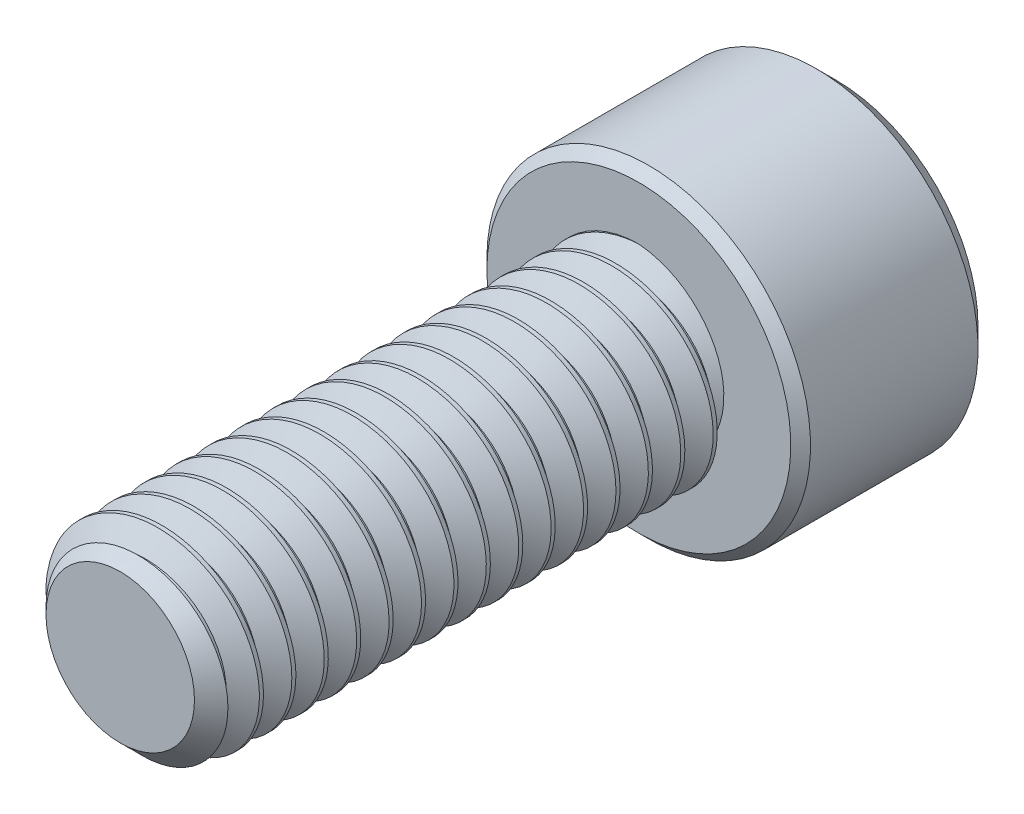
SolidWorks part; units mm, degrees
material "Cast Alloy Steel"
ref_plane "Front Plane" through (0, 0, 0) normal (0, 0, 1) x (1, 0, 0)
ref_plane "Top Plane" through (0, 0, 0) normal (0, 1, 0) x (1, 0, 0)
ref_plane "Right Plane" through (0, 0, 0) normal (1, 0, 0) x (0, 0, -1)
sketch "Sketch1" plane through (0, 0, 0) normal (0, 0, 1) x (1, 0, 0)
  line L0 (0, 2.413) -> (0, -2.413) construction
  circle A0 centre (0, 0) radius 2.413
  dimension "OD" = 4.826
extrude "Extrude1" add sketch "Sketch1" against normal blind 12.7
sketch "Sketch2" plane through (0, 0, 0) normal (0, 0, 1) x (1, 0, 0)
  circle A0 centre (0, 0) radius 2.413 construction
  circle A1 centre (0, 0) radius 2.413
curve "Helix/Spiral1" pitch 0.7937 height 13.4937 turns 17 parameters "pitch"=0.7937
chamfer "Chamfer3" distance 0.5953 angle 45 1 edges at (2.413, 0, 0)
sketch "Sketch3" plane through (0, 0, 0) normal (1, 0, 0) x (0, 0, -1)
  line L0 (-0.6945, 2.413) -> (-0.3969, 1.8974)
  line L1 (-0.3969, 1.8974) -> (-0.2977, 1.8974)
  line L2 (-0.2977, 1.8974) -> (0, 2.413)
  line L3 (-0.6945, 2.413) -> (0, 2.413)
  line L4 (-0.3473, 2.413) -> (-0.3473, 1.8974) construction
  line L5 (-0.5457, 2.1552) -> (-0.1488, 2.1552) construction
  line L6 (0, 2.413) -> (0, -2.413) construction
  dimension "D1" = 0.0992
  dimension "D2" = 0.3969
  dimension "D3" = 60
sweep "Cut-Sweep1" cut profiles "Sketch3" path "Helix/Spiral1"
sketch "Sketch6" plane through (0, 0, -12.7) normal (0, 0, -1) x (-1, 0, 0)
  circle A0 centre (0, 0) radius 3.9624
  dimension "head dia" = 7.9248
extrude "Extrude2" add sketch "Sketch6" along normal blind 4.826
sketch "Sketch7" plane through (0, 0, -17.526) normal (0, 0, -1) x (-1, 0, 0)
  line L1 (0, 2.2914) -> (-1.9844, 1.1457)
  line L2 (-1.9844, 1.1457) -> (-1.9844, -1.1457)
  line L3 (-1.9844, -1.1457) -> (0, -2.2914)
  line L4 (0, -2.2914) -> (1.9844, -1.1457)
  line L5 (1.9844, -1.1457) -> (1.9844, 1.1457)
  line L6 (1.9844, 1.1457) -> (0, 2.2914)
  circle A0 centre (0, 0) radius 1.9844 construction
  dimension "hex dia" = 3.9688
extrude "Cut-Extrude1" cut sketch "Sketch7" against normal blind 2.9766
sketch "Sketch8" plane through (0, 0, -17.526) normal (0, 0, -1) x (-1, 0, 0)
  circle A0 centre (0, 0) radius 2.2914
extrude "Cut-Extrude2" cut sketch "Sketch8" against normal blind 0.4826 draft 45
chamfer "Chamfer1" distance 0.4826 angle 45 1 edges at (-3.9624, 0, -17.526)
chamfer "Chamfer2" distance 0.2413 angle 45 1 edges at (-3.9624, 0, -12.7)
sketch "Sketch9" plane through (0, 0, 0) normal (1, 0, 0) x (0, 0, -1)
  line L0 (0, 2.413) -> (0, -2.413) construction
  line L1 (4.3656, 2.413) -> (4.3656, -2.413) construction
  line L2 (12.7, 3.9624) -> (12.7, -3.9624) construction
  line L3 (17.526, 3.9624) -> (17.526, -3.9624) construction
  line L4 (17.526, 0) -> (0, 0) construction
  dimension "D1" = 4.3656
  dimension "D2" = 4.826
  dimension "D3" = 7.9248
  dimension "D4" = 12.7
equation "\"D3@Helix/Spiral1\" = \"screw length@Extrude1\"+\"pitch@Helix/Spiral1\""
equation "\"D1@Sketch3\" = \"pitch@Helix/Spiral1\"*.125"
equation "\"D2@Sketch3\" = \"pitch@Helix/Spiral1\"*.5"
equation "\"D1@Cut-Extrude1\" = \"hex dia@Sketch7\"*.75"
equation "\"D1@Chamfer1\" = \"head depth@Extrude2\"/10"
equation "\"D1@Sketch9\" = \"pitch@Helix/Spiral1\"*5.5"
equation "\"D1@Chamfer2\" = \"D1@Chamfer1\"/2"
equation "\"D1@Cut-Extrude2\" = \"D1@Chamfer2\"*2"
equation "\"D1@Chamfer3\" = \"pitch@Helix/Spiral1\"*.750"
equation "\"D2@Sketch9\" = \"head depth@Extrude2\""
equation "\"D3@Sketch9\" = \"head dia@Sketch6\""
equation "\"D4@Sketch9\" = \"screw length@Extrude1\""
